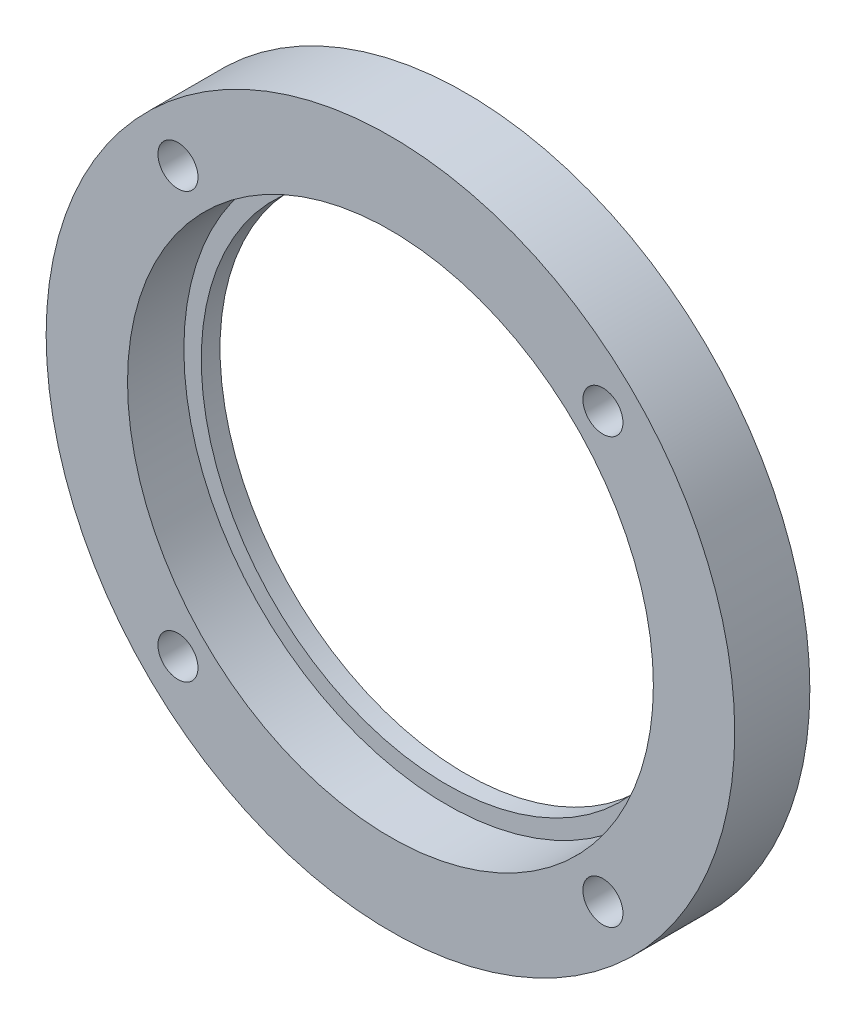
SolidWorks part; units mm, degrees
material "3.1325 (EN-AW 2017A)"
ref_plane "正面" through (0, 0, 0) normal (0, 0, 1) x (1, 0, 0)
ref_plane "平面" through (0, 0, 0) normal (0, 1, 0) x (1, 0, 0)
ref_plane "右側面" through (0, 0, 0) normal (1, 0, 0) x (0, 0, -1)
sketch "ｽｹｯﾁ1" plane through (0, 0, 0) normal (0, 0, 1) x (1, 0, 0)
  line L0 (0, 0) -> (0, -50000) construction
  circle A0 centre (0, 0) radius 27.5
  circle A1 centre (0, 0) radius 19.61
  circle A2 centre (0, 0) radius 21
  circle A3 centre (0, 0) radius 24 construction
  point P2 (16.9706, 16.9706)
  point P10 (16.9706, -16.9706)
  point P11 (-16.9706, -16.9706)
  point P12 (-16.9706, 16.9706)
  point P13 (0, 0)
  dimension "D1" = 55
  dimension "D2" = 42
  dimension "D3" = 39.22
  dimension "D4" = 48
  dimension "D5" = 4
extrude "ﾎﾞｽ - 押し出し1" add sketch "ｽｹｯﾁ1" along normal blind 6 contours A0 A2 region at (-26.7222, 0, 0)
extrude "ﾎﾞｽ - 押し出し2" add sketch "ｽｹｯﾁ1<3>" along normal blind 1.5 contours A2 A1 region at (-20.406, 0, 0)
sketch "ｽｹｯﾁ1<3>" plane through (0, 0, 0) normal (0, 0, 1) x (1, 0, 0) same geometry as "ｽｹｯﾁ1"
hole_wizard "M3 丸皿ねじ用皿穴1" positions "3Dｽｹｯﾁ1" profile "ｽｹｯﾁ2" countersink size "M3" standard "JIS" end condition through all
sketch3d "3Dｽｹｯﾁ1"
  point P0 (16.9706, 16.9706, 0)
  point P2 (-16.9706, 16.9706, 0)
  point P4 (-16.9706, -16.9706, 0)
  point P6 (16.9706, -16.9706, 0)
sketch "ｽｹｯﾁ2" plane through (16.9706, 16.9706, 0) normal (1, 0, 0) x (0, 1, 0)
  line L0 (0, 0) -> (0, 6)
  line L1 (0, 6) -> (1.6, 6)
  line L2 (1.6, 6) -> (1.6, 1.55)
  line L3 (1.6, 1.55) -> (3.15, 0)
  line L5 (3.15, 0) -> (0, 0)
  line L6 (-1.6, 1.55) -> (-3.15, 0) construction
  line L11 (0, -6.35) -> (0, 107.95) construction
  dimension "通し穴の直径" = 3.2
  dimension "通し穴の深さ" = 6
  dimension "表面の皿穴の直径" = 6.3
  dimension "表面の皿穴の角度" = 90
